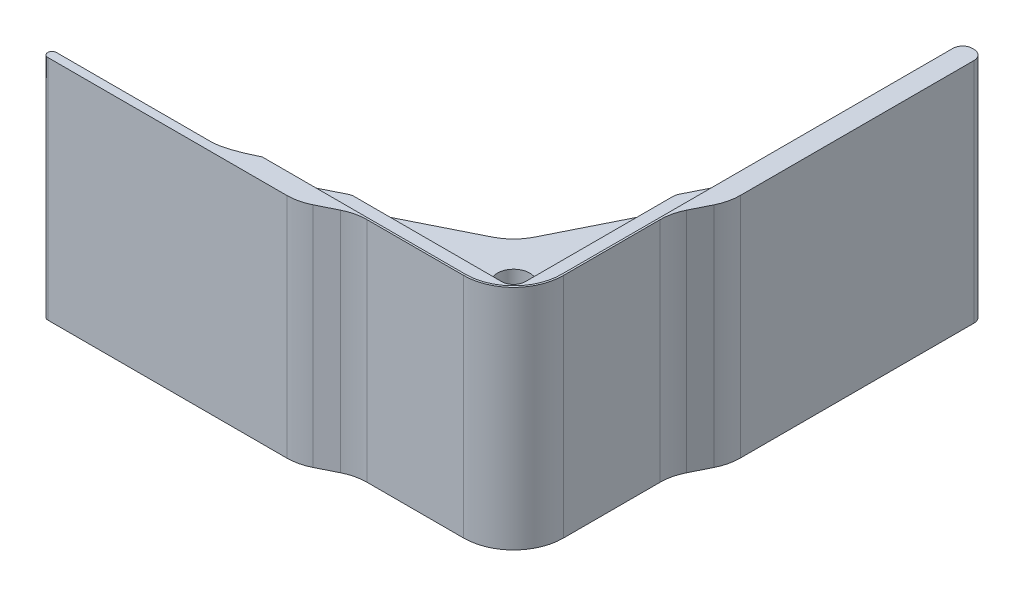
SolidWorks part; units mm, degrees
material "Nylon 101"
ref_plane "Front Plane" through (0, 0, 0) normal (0, 0, 1) x (1, 0, 0)
ref_plane "Top Plane" through (0, 0, 0) normal (0, 1, 0) x (1, 0, 0)
ref_plane "Right Plane" through (0, 0, 0) normal (1, 0, 0) x (0, 0, -1)
sketch "Sketch1" plane through (0, 0, 0) normal (0, 1, 0) x (1, 0, 0)
  line L0 (0, -18.288) -> (-106.3752, -18.288)
  line L1 (18.288, 0) -> (18.288, 106.3752)
  line L2 (-106.3752, -18.288) -> (-106.3752, -12.7)
  line L3 (-106.3752, -12.7) -> (0, -12.7)
  line L4 (12.7, 0) -> (12.7, 106.3752)
  line L5 (12.7, 106.3752) -> (18.288, 106.3752)
  line L6 (-5.6667, 11.3657) -> (-53.935, -12.7)
  line L7 (-11.3657, 5.6667) -> (12.7, 53.935)
  circle A0 centre (0, 0) radius 4.2862
  arc A1 (0, -18.288) -> (18.288, 0) centre (0, 0) ccw
  circle A2 centre (0, 0) radius 12.7
  dimension "D1" = 8.5725
  dimension "D2" = 25.4
  dimension "D4" = 5.588
  dimension "D5" = 106.3752
  dimension "D6" = 26.5
  dimension "D3" = 12.7
extrude "Boss-Extrude1" add sketch "Sketch1" along normal blind 50.8 contours A2 L3 L2 L0 A1 L1 L5 L4 | A2 A0 | A2 L3 | A2 L4 L7 | A2 L6 L7 region at (-53.1876, 0, 16.525) region at (-24.9461, 0, 5.9194) region at (-10.494, 0, 6.4939) region at (5.9194, 0, -24.9461) region at (-9.0813, 0, -9.0813)
fillet "Fillet8" radius 12.7 2 edges at (-9.4696, 25.4, -9.4696) (12.7, 25.4, -53.935)
sketch "Sketch2" plane through (0, 50.8, 0) normal (0, 1, 0) x (1, 0, 0)
  line L0 (-106.3752, -12.7) -> (-53.935, -12.7) construction
  line L1 (-64.262, -12.7) -> (-106.3752, -12.7)
  line L2 (-64.262, -12.7) -> (-64.262, -16.002)
  line L3 (-64.262, -16.002) -> (-106.3752, -16.002)
  line L4 (-106.3752, -12.7) -> (-106.3752, -16.002)
  line L8 (-60.5578, -16.002) -> (-64.262, -16.002)
  line L12 (18.288, 0) -> (18.288, 106.3752) construction
  line L13 (-106.3752, -18.288) -> (-106.3752, -12.7) construction
  line L14 (-13.2725, 7.5736) -> (-53.935, -12.7) construction
  line L15 (-13.2725, 7.5736) -> (-60.5578, -16.002)
  conic Q0 (-53.935, -12.7) -> (-64.262, -16.002) control (-60.5578, -16.002) rho 0.5
  line M11 (-53.935, -12.7) -> (-106.3752, -12.7)
  line M13 (-106.3752, -12.7) -> (-106.3752, -18.288)
  dimension "D1" = 82.55
  dimension "D6" = 3.302
extrude "Cut-Extrude1" cut sketch "Sketch2" against normal through all contours L3 L2 M11 M13 | L2 region at (-85.3186, 50.8, 14.351) region at (-60.5438, 50.8, 13.9706)
fillet "Fillet3" radius 2.54 2 edges at (18.288, 25.4, -106.3752) (12.7, 25.4, -106.3752)
fillet "Fillet6" 2 edges at (-106.3752, 25.4, 18.288) (-106.3752, 25.4, 16.002) type full round first side face at (-53.1876, 25.4, 18.288) second side face at (-85.3186, 25.4, 16.002) middle face at (-106.3752, 25.4, 17.145)
ref_plane "Plane1" through (0, 25.4, 0) normal (0, 1, 0) x (1, 0, 0)
sketch "Sketch3" plane through (0, 25.4, 0) normal (0, 1, 0) x (1, 0, 0)
  line L2 (15.748, 106.3752) -> (15.24, 106.3752)
  line L3 (15.748, 106.3752) -> (15.24, 106.3752)
  line L4 (0, -12.7) -> (-53.935, -12.7)
  line L11 (12.7, 103.8352) -> (12.7, 56.9254)
  line L18 (12.7, 103.8352) -> (12.7, 0)
  line L19 (-105.2322, -18.288) -> (0, -18.288)
  line L20 (-105.2322, -18.288) -> (0, -18.288)
  line L22 (18.288, 0) -> (18.288, 103.8352)
  line L23 (18.288, 0) -> (18.288, 103.8352)
  line L24 (11.3657, 51.2587) -> (-7.5736, 13.2725)
  line L25 (-13.2725, 7.5736) -> (-53.935, -12.7)
  line L26 (-64.262, -16.002) -> (-105.2322, -16.002)
  line L27 (-64.262, -16.002) -> (-105.2322, -16.002)
  arc A0 (0, -12.7) -> (12.7, 0) centre (0, 0) ccw
  circle A1 centre (0, 0) radius 4.2862 construction
  arc A13 (0, -18.288) -> (18.288, 0) centre (0, 0) ccw
  arc A14 (0, -18.288) -> (18.288, 0) centre (0, 0) ccw
  arc A15 (11.3657, 51.2587) -> (12.7, 56.9254) centre (0, 56.9254) ccw
  arc A25 (-13.2725, 7.5736) -> (-7.5736, 13.2725) centre (-18.9392, 18.9392) ccw
  arc A29 (-105.2322, -16.002) -> (-105.2322, -18.288) centre (-105.2322, -17.145) ccw
  arc A30 (-105.2322, -16.002) -> (-105.2322, -18.288) centre (-105.2322, -17.145) ccw
  arc A31 (18.288, 103.8352) -> (15.748, 106.3752) centre (15.748, 103.8352) ccw
  arc A32 (18.288, 103.8352) -> (15.748, 106.3752) centre (15.748, 103.8352) ccw
  arc A33 (15.24, 106.3752) -> (12.7, 103.8352) centre (15.24, 103.8352) ccw
  arc A34 (15.24, 106.3752) -> (12.7, 103.8352) centre (15.24, 103.8352) ccw
  parabola Q0 (-53.935, -12.7) -> (-64.262, -16.002) focus (-66.324, -13.6691) apex (-67.4816, -14.9788) construction
  parabola Q1 (-53.935, -12.7) -> (-64.262, -16.002) focus (-66.324, -13.6691) apex (-67.4816, -14.9788)
  parabola Q2 (-53.935, -12.7) -> (-64.262, -16.002) focus (-66.324, -13.6691) apex (-67.4816, -14.9788)
  dimension "D1" = 0
extrude "Boss-Extrude2" add sketch "Sketch3" along normal mid plane 60.325
sketch "Sketch6" plane through (0, 55.5625, 0) normal (0, 1, 0) x (1, 0, 0)
  line L1 (18.288, -18.288) -> (-38.862, -18.288)
  line L2 (18.288, -18.288) -> (18.288, -13.081)
  line L3 (0, -13.208) -> (-38.862, -13.208)
  line L4 (-38.862, -18.288) -> (-38.862, -13.208)
  line L5 (13.081, -18.288) -> (18.288, -18.288)
  line L6 (13.208, 0) -> (13.208, 38.862)
  line L7 (13.208, 38.862) -> (18.288, 38.862)
  line L8 (18.288, -18.288) -> (18.288, 38.862)
  line L10 (-38.862, -18.288) -> (-28.6731, -13.208)
  line L11 (18.288, 38.862) -> (13.208, 28.6731)
  line L13 (0, -18.288) -> (-105.2322, -18.288) construction
  line L14 (-13.2725, 7.5736) -> (-53.935, -12.7) construction
  line L15 (-7.5736, 13.2725) -> (11.3657, 51.2587) construction
  arc A2 (0, -13.208) -> (13.208, 0) centre (0, 0) ccw
  arc A3 (0, -13.208) -> (13.208, 0) centre (0, 0) ccw
  arc M17 (0, -18.288) -> (18.288, 0) centre (0, 0) ccw
  line M18 (18.288, 0) -> (18.288, 103.8352)
  dimension "D2" = 57.15
  dimension "D3" = 5.08
extrude "Cut-Extrude2" cut sketch "Sketch6" against normal through all contours L11 L6 M18 M17 region at (-19.431, 55.5625, 17.4798)
fillet "Fillet7" radius 12.7 4 edges at (-28.6731, 25.4, 13.208) (13.208, 25.4, -28.6731) (18.288, 25.4, -38.862) (-38.862, 25.4, 18.288)
sketch "Sketch7" plane through (0, 50.8, 0) normal (0, 1, 0) x (1, 0, 0)
  line L1 (4.826, -4.826) -> (-38.1422, -4.826)
  line L2 (4.826, -4.826) -> (4.826, 38.1422)
  line L3 (4.826, 38.1422) -> (-38.1422, 38.1422)
  line L4 (-38.1422, -4.826) -> (-38.1422, 38.1422)
  line L6 (-13.2725, 7.5736) -> (-53.935, -12.7) construction
  arc A0 (-2.7214, -3.9084) -> (3.9084, 2.7214) centre (0, 0) ccw construction
  dimension "D1" = 4.826
  dimension "D2" = 4.826
extrude "Cut-Extrude3" cut sketch "Sketch7" against normal blind 3.429
fillet "Fillet9" radius 3.175 3 edges at (4.826, 49.0855, -38.1422) (4.826, 49.0855, 4.826) (-38.1422, 49.0855, 4.826)
equation "\"D1@Sketch1\"=.3125+0.025"
equation "\"D2@Sketch7\"=\"D1@Sketch7\""
